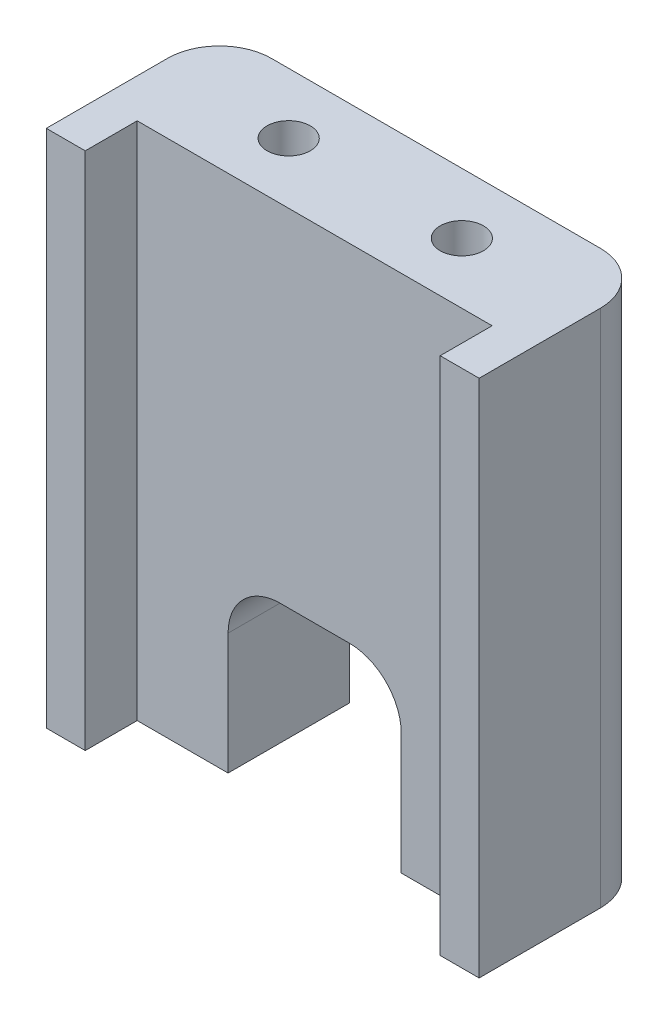
SolidWorks part; units mm, degrees
ref_plane "정면" through (0, 0, 0) normal (0, 0, 1) x (1, 0, 0)
ref_plane "윗면" through (0, 0, 0) normal (0, 1, 0) x (1, 0, 0)
ref_plane "우측면" through (0, 0, 0) normal (1, 0, 0) x (0, 0, -1)
sketch "스케치1" plane through (0, 0, 0) normal (0, 0, 1) x (1, 0, 0)
  line L1 (0, 0) -> (25, 0)
  line L2 (0, 0) -> (0, 30)
  line L3 (0, 30) -> (25, 30)
  line L4 (25, 0) -> (25, 30)
  dimension "D1" = 30
  dimension "D2" = 25
extrude "보스-돌출1" add sketch "스케치1" along normal blind 10
sketch "스케치2" plane through (0, 0, 10) normal (0, 0, 1) x (1, 0, 0)
  line L0 (25, 30) -> (0, 30) construction
  line L1 (2.25, 30) -> (22.75, 30)
  line L2 (2.25, 30) -> (2.25, 0)
  line L3 (2.25, 0) -> (22.75, 0)
  line L4 (22.75, 30) -> (22.75, 0)
  line L5 (0, 0) -> (25, 0) construction
  line L7 (0, 30) -> (0, 0) construction
  dimension "D1" = 20.5
  dimension "D2" = 2.25
extrude "컷-돌출1" cut sketch "스케치2" against normal blind 3
sketch "스케치3" plane through (0, 30, 0) normal (0, 1, 0) x (1, 0, 0)
  line L0 (7.5, -3.5) -> (17.5, -3.5) construction
  line L1 (25, 0) -> (0, 0) construction
  circle A0 centre (7.5, -3.5) radius 1.25
  circle A1 centre (17.5, -3.5) radius 1.25
  point P6 (12.5, 0)
  point P7 (12.5, -3.5)
  dimension "D2" = 10
  dimension "D3" = 2.5
  dimension "D1" = 3.5
extrude "컷-돌출2" cut sketch "스케치3" against normal blind 12
sketch "스케치4" plane through (0, 0, 0) normal (0, -1, 0) x (1, 0, 0)
  line L0 (3.5, 3.5) -> (21.5, 3.5) construction
  line L1 (0, 0) -> (25, 0) construction
  circle A0 centre (3.5, 3.5) radius 1.25
  circle A1 centre (21.5, 3.5) radius 1.25
  point P4 (12.5, 0)
  point P5 (12.5, 3.5)
  dimension "D2" = 2.5
  dimension "D3" = 3.5
  dimension "D1" = 18
extrude "컷-돌출3" cut sketch "스케치4" against normal blind 12
sketch "스케치5" plane through (0, 0, 0) normal (0, 0, -1) x (-1, 0, 0)
  line L0 (0, 0) -> (-25, 0) construction
  line L1 (-17.5, 0) -> (-7.5, 0)
  line L2 (-17.5, 0) -> (-17.5, 10)
  line L3 (-17.5, 10) -> (-7.5, 10)
  line L4 (-7.5, 0) -> (-7.5, 10)
  line L5 (0, 30) -> (0, 0) construction
  dimension "D1" = 10
  dimension "D2" = 10
  dimension "D3" = 7.5
extrude "컷-돌출4" cut sketch "스케치5" against normal blind 12
fillet "필렛1" radius 3 4 edges at (7.5, 10, 3.5) (17.5, 10, 3.5) (0, 15, 0) (25, 15, 0)
